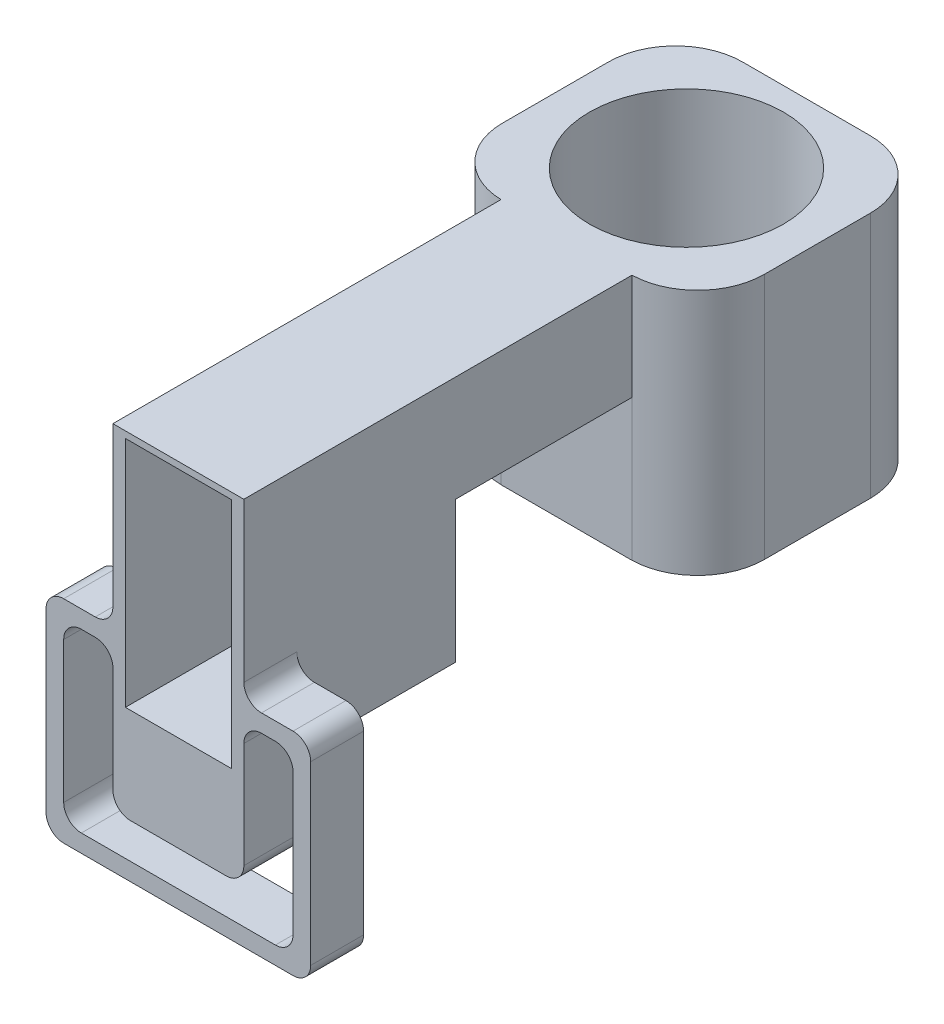
SolidWorks part; units mm, degrees
ref_plane "Front Plane" through (0, 0, 0) normal (0, 0, 1) x (1, 0, 0)
ref_plane "Top Plane" through (0, 0, 0) normal (0, 1, 0) x (1, 0, 0)
ref_plane "Right Plane" through (0, 0, 0) normal (1, 0, 0) x (0, 0, -1)
sketch "Sketch1" plane through (0, 0, 0) normal (0, 1, 0) x (1, 0, 0)
  line L0 (-74.2237, 0) -> (-37.1118, -68) construction
  line L1 (0, 0) -> (-74.2237, 0)
  line L2 (0, 0) -> (0, -68)
  line L3 (0, -68) -> (-74.2237, -68)
  line L4 (-74.2237, 0) -> (-74.2237, -68)
  line L5 (-37.1118, -68) -> (0, 0) construction
  line L6 (-55.6678, -34) -> (-55.6678, -68) construction
  line L7 (-18.5559, -34) -> (-18.5559, -68) construction
  line L8 (-55.6678, -68) -> (-55.6678, -120)
  line L9 (-55.6678, -120) -> (-18.5559, -120)
  line L10 (-18.5559, -120) -> (-18.5559, -68)
  line L12 (-18.5559, -120) -> (-55.6678, -120)
  line L13 (-18.5559, -120) -> (-18.5559, -178)
  line L14 (-18.5559, -178) -> (-55.6678, -178)
  line L15 (-55.6678, -120) -> (-55.6678, -178)
  dimension "D1" = 120
  dimension "D2" = 68
  dimension "D3" = 58
  dimension "D4" = 18.5559
extrude "Boss-Extrude1" add sketch "Sketch1" against normal blind 70 contours L1 L4 L3 L2 | L9 L10 L3 L8 | L9 L15 L14 L13 region at (-37.1118, 0, 34) region at (-37.1118, 0, 94) region at (-37.1118, 0, 149)
sketch "Sketch2" plane through (0, 0, 0) normal (0, 1, 0) x (1, 0, 0)
  line L0 (-55.6678, -68) -> (-18.5559, -68) construction
  line L1 (-37.1118, -68) -> (-37.1118, 0) construction
  line L2 (0, 0) -> (-74.2237, 0) construction
  circle A0 centre (-37.1118, -34) radius 27.5
  dimension "D1" = 55
extrude "Cut-Extrude1" cut sketch "Sketch2" against normal blind 70
fillet "Fillet1" radius 19 4 edges at (0, -35, 68) (0, -35, 0) (-74.2237, -35, 68) (-74.2237, -35, 0)
sketch "Sketch3" plane through (0, 0, 178) normal (0, 0, 1) x (1, 0, 0)
  line L0 (-18.5559, 0) -> (-55.6678, 0) construction
  line L1 (-20.5559, -3.7111) -> (-53.6678, -3.7111)
  line L2 (-20.5559, -3.7111) -> (-20.5559, -68)
  line L3 (-20.5559, -68) -> (-53.6678, -68)
  line L4 (-53.6678, -3.7111) -> (-53.6678, -68)
  line L5 (-18.5559, -70) -> (-55.6678, -70) construction
  line L6 (-55.6678, -70) -> (-55.6678, 0) construction
  line L7 (-18.5559, -70) -> (-18.5559, 0) construction
  dimension "D1" = 3.7111
  dimension "D2" = 2
  dimension "D3" = 2
  dimension "D4" = 2
extrude "Cut-Extrude2" cut sketch "Sketch3" against normal blind 58
sketch "Sketch5" plane through (-55.6678, 0, 0) normal (-1, 0, 0) x (0, 0, 1)
  line L0 (68, 0) -> (178, 0) construction
  line L1 (68, -70) -> (118, -70)
  line L2 (68, -70) -> (68, -30)
  line L3 (68, -30) -> (118, -30)
  line L4 (118, -70) -> (118, -30)
  line L5 (120, -3.7111) -> (120, -68) construction
  dimension "D1" = 30
  dimension "D2" = 2
extrude "Cut-Extrude3" cut sketch "Sketch5" against normal blind 58
sketch "Sketch7" plane through (0, 0, 118) normal (0, 0, -1) x (-1, 0, 0)
  line L0 (18.5559, -70) -> (55.6678, -70) construction
  line L1 (22.5559, -41.3697) -> (52.0723, -41.3697)
  line L2 (22.5559, -41.3697) -> (22.5559, -60)
  line L3 (22.5559, -60) -> (52.0723, -60)
  line L4 (52.0723, -41.3697) -> (52.0723, -60)
  line L5 (55.6678, -70) -> (55.6678, -30) construction
  line L6 (20.5559, -68) -> (20.5559, -3.7111) construction
  dimension "D1" = 10
  dimension "D2" = 3.5955
  dimension "D3" = 2
extrude "Cut-Extrude5" cut sketch "Sketch7" against normal blind 58
sketch "Sketch8" plane through (0, 0, 178) normal (0, 0, 1) x (1, 0, 0)
  line L1 (-53.6678, -3.7111) -> (-20.5559, -3.7111)
  line L2 (-53.6678, -3.7111) -> (-53.6678, -1.7111)
  line L3 (-53.6678, -1.7111) -> (-20.5559, -1.7111)
  line L4 (-20.5559, -3.7111) -> (-20.5559, -1.7111)
  dimension "D1" = 2
extrude "Cut-Extrude6" cut sketch "Sketch8" against normal blind 58
sketch "Sketch9" plane through (0, 0, 178) normal (0, 0, 1) x (1, 0, 0)
  line L0 (-20.5559, -1.7111) -> (-53.6678, -1.7111) construction
  line L1 (-53.6678, -68) -> (-52.1178, -68)
  line L2 (-53.6678, -68) -> (-53.6678, -1.7111)
  line L3 (-53.6678, -1.7111) -> (-52.1178, -1.7111)
  line L4 (-52.1178, -68) -> (-52.1178, -1.7111)
  line L6 (-20.5559, -68) -> (-22.1059, -68)
  line L7 (-20.5559, -68) -> (-20.5559, -1.7111)
  line L8 (-20.5559, -1.7111) -> (-22.1059, -1.7111)
  line L9 (-22.1059, -68) -> (-22.1059, -1.7111)
  dimension "D1" = 1.55
  dimension "D2" = 1.55
extrude "Boss-Extrude2" add sketch "Sketch9" against normal blind 58
sketch "Sketch10" plane through (0, 0, 178) normal (0, 0, 1) x (1, 0, 0)
  line L0 (-22.1059, -1.7111) -> (-22.1059, -68) construction
  line L1 (-52.1178, -68) -> (-22.1059, -68)
  line L2 (-52.1178, -68) -> (-52.1178, -67.855)
  line L3 (-52.1178, -67.855) -> (-22.1059, -67.855)
  line L4 (-22.1059, -68) -> (-22.1059, -67.855)
  line L6 (-52.1178, -1.7111) -> (-22.1059, -1.7111)
  line L7 (-52.1178, -1.7111) -> (-52.1178, -1.8561)
  line L8 (-52.1178, -1.8561) -> (-22.1059, -1.8561)
  line L9 (-22.1059, -1.7111) -> (-22.1059, -1.8561)
  dimension "D1" = 0.145
  dimension "D2" = 0.145
extrude "Boss-Extrude3" add sketch "Sketch10" against normal blind 58
sketch "Sketch11" plane through (0, 0, 178) normal (0, 0, 1) x (1, 0, 0)
  line L0 (-37.1118, 0) -> (-37.1118, -50) construction
  line L1 (-18.5559, 0) -> (-55.6678, 0) construction
  line L2 (-74.6118, -79.9416) -> (-69.6118, -79.9416) construction
  line L3 (-4.6118, -79.9416) -> (0.3882, -79.9416) construction
  line L4 (-74.6118, -49.9416) -> (-74.6118, -109.9416)
  line L5 (-74.6118, -109.9416) -> (0.3882, -109.9416)
  line L6 (0.3882, -49.9416) -> (0.3882, -109.9416)
  line L7 (-4.6118, -54.9416) -> (-18.5559, -54.9416)
  line L8 (-69.6118, -104.9416) -> (-4.6118, -104.9416)
  line L9 (-69.6118, -104.9416) -> (-69.6118, -54.9416)
  line L10 (-18.5559, -54.9416) -> (-18.5559, -49.9416)
  line L11 (-4.6118, -104.9416) -> (-4.6118, -54.9416)
  line L12 (-55.6678, -54.9416) -> (-69.6118, -54.9416)
  line L14 (-18.5559, -49.9416) -> (0.3882, -49.9416)
  line L15 (-18.5559, -70) -> (-55.6678, -70)
  line L16 (-18.5559, -70) -> (-18.5559, -94.9416)
  line L17 (-55.6678, -54.9416) -> (-55.6678, -49.9416)
  line L18 (-55.6678, -49.9416) -> (-74.6118, -49.9416)
  line L19 (-37.1118, 0) -> (-37.1118, -115.0475) construction
  line L20 (-18.5559, -94.9416) -> (-55.6678, -94.9416)
  line L21 (-55.6678, -70) -> (-55.6678, -94.9416)
  point P4 (-37.1118, -67.4894)
  point P7 (-37.1118, -79.9416)
  dimension "D1" = 60
  dimension "D2" = 75
  dimension "D3" = 5
  dimension "D4" = 50
  dimension "D5" = 5
  dimension "D6" = 10
extrude "Boss-Extrude5" add sketch "Sketch11" against normal blind 15
fillet "Fillet3" radius 5 10 edges at (0.3882, -49.9416, 170.5) (-4.6118, -54.9416, 170.5) (-74.6118, -49.9416, 170.5) (-69.6118, -54.9416, 170.5) (-69.6118, -104.9416, 170.5) (-4.6118, -104.9416, 170.5) (-55.6678, -94.9416, 170.5) (-18.5559, -94.9416, 170.5) (-74.6118, -109.9416, 170.5) (0.3882, -109.9416, 170.5)
fillet "Fillet4" radius 5 2 edges at (-55.6678, -54.9416, 170.5) (-18.5559, -54.9416, 170.5)
fillet "Fillet5" radius 5 2 edges at (-18.5559, -49.9416, 170.5) (-55.6678, -49.9416, 170.5)
